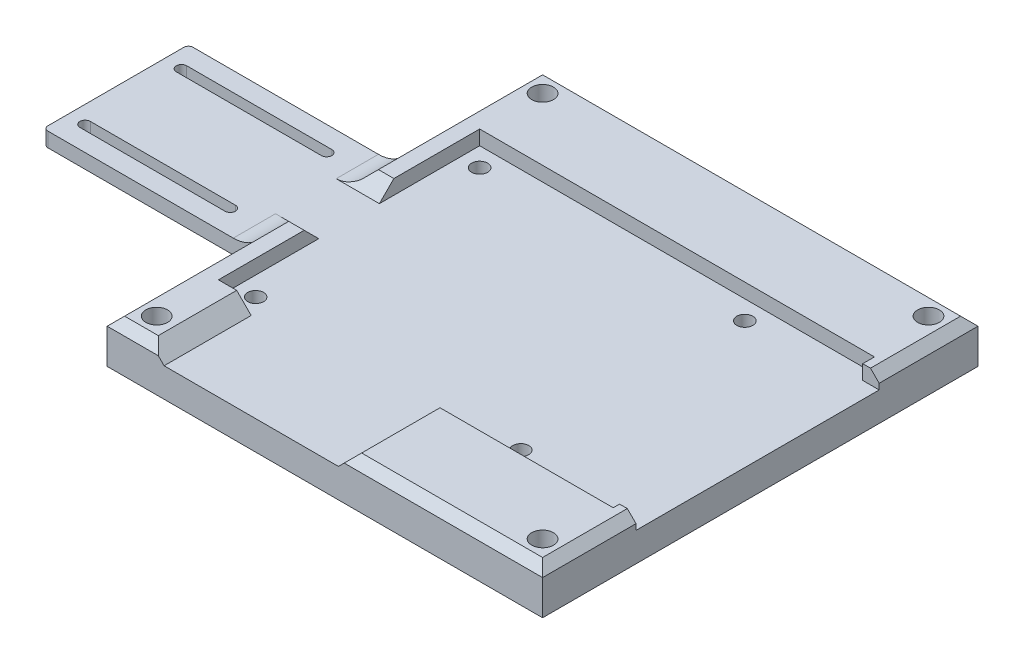
SolidWorks part; units mm, degrees
material "ABS"
ref_plane "Front Plane" through (0, 0, 0) normal (0, 0, 1) x (1, 0, 0)
ref_plane "Top Plane" through (0, 0, 0) normal (0, 1, 0) x (1, 0, 0)
ref_plane "Right Plane" through (0, 0, 0) normal (1, 0, 0) x (0, 0, -1)
sketch "Sketch1" plane through (0, 0, 0) normal (0, 1, 0) x (1, 0, 0)
  line L1 (-47.625, 47.625) -> (47.625, 47.625)
  line L2 (-47.625, 47.625) -> (-47.625, -47.625)
  line L3 (-47.625, -47.625) -> (47.625, -47.625)
  line L4 (47.625, 47.625) -> (47.625, -47.625)
  line L5 (-47.625, 47.625) -> (47.625, -47.625) construction
  line L6 (-47.625, -47.625) -> (47.625, 47.625) construction
  point P0 (0, 0)
  dimension "D1" = 95.25
  dimension "D2" = 95.25
extrude "Base Extrude" add sketch "Sketch1" along normal blind 6.35
sketch "Sketch2" plane through (0, 6.35, 0) normal (0, 1, 0) x (1, 0, 0)
  line L0 (-47.625, 0) -> (47.625, 0) construction
  line L1 (-42.3368, -28.575) -> (-34.5346, -28.575)
  line L2 (-42.3368, -28.575) -> (-42.3368, -6)
  line L3 (-42.3368, 28.575) -> (44.0232, 28.575)
  line L4 (44.0232, -28.575) -> (44.0232, -27.1833)
  line L5 (-47.625, 47.625) -> (-47.625, -47.625) construction
  line L6 (47.625, -47.625) -> (47.625, 47.625) construction
  line L7 (-42.3368, 6) -> (-47.625, 6)
  line L8 (-47.625, 47.625) -> (47.625, 47.625)
  line L9 (-47.625, 47.625) -> (-47.625, -47.625)
  line L10 (-47.625, -47.625) -> (47.625, -47.625)
  line L11 (47.625, 47.625) -> (47.625, -47.625)
  line L12 (-42.3368, -6) -> (-47.625, -6)
  line L13 (-47.625, -6) -> (-47.625, 6)
  line L14 (-42.3368, 6) -> (-42.3368, 28.575)
  line L15 (44.0232, 26.0091) -> (47.625, 26.0091)
  line L16 (44.0232, -27.1833) -> (47.625, -27.1833)
  line L17 (47.625, 26.0091) -> (47.625, -27.1833)
  line L18 (44.0232, 26.0091) -> (44.0232, 28.575)
  line L19 (-34.5346, -28.575) -> (-34.5346, -50.5748)
  line L20 (2.3256, -28.575) -> (2.3256, -50.5748)
  line L21 (2.3256, -50.5748) -> (-34.5346, -50.5748)
  line L22 (2.3256, -28.575) -> (44.0232, -28.575)
  point P24 (-47.625, 0)
  line M6 (47.625, -47.625) -> (47.625, 47.625)
  line M7 (47.625, 47.625) -> (-47.625, 47.625)
  line M8 (-47.625, 47.625) -> (-47.625, -47.625)
  line M9 (-47.625, -47.625) -> (47.625, -47.625)
  dimension "D1" = 86.36
  dimension "D2" = 57.15
  dimension "D3" = 12
  dimension "D4" = 53.1924
extrude "Pi Slot" add sketch "Sketch2" along normal blind 3.175 contours L19 L1 L2 L12 L9 M9 | L22 L20 L16 L4 M9 M6 | L18 L15 L11 L7 L14 L3 M7 M8
chamfer "Chamfer1" distance 3.81 angle 45 4 edges at (2.3256, 9.525, 38.1) (-34.5346, 9.525, 38.1) (-44.9809, 9.525, 6) (-44.9809, 9.525, -6)
chamfer "Chamfer2" distance 1.905 angle 45 7 edges at (47.625, 9.525, -36.8171) (0, 9.525, -47.625) (-47.625, 9.525, -28.7175) (-47.625, 9.525, 28.7175) (-42.9848, 9.525, 47.625) (47.625, 9.525, 37.4041) (26.8803, 9.525, 47.625)
sketch "Sketch3" plane through (0, 0, 0) normal (0, 1, 0) x (1, 0, 0)
  line L0 (-47.625, -47.625) -> (-47.625, -7.905) construction
  line L1 (-93.345, 15.875) -> (-47.625, 15.875)
  line L2 (-93.345, 15.875) -> (-93.345, -15.875)
  line L3 (-93.345, -15.875) -> (-47.625, -15.875)
  line L4 (-47.625, 15.875) -> (-47.625, -15.875)
  line L5 (-93.345, 15.875) -> (-47.625, -15.875) construction
  line L6 (-93.345, -15.875) -> (-47.625, 15.875) construction
  line L7 (-47.625, 0) -> (-93.345, 0) construction
  line L8 (-89.535, 10.541) -> (-57.785, 10.541) construction
  line L9 (-89.535, 11.684) -> (-57.785, 11.684)
  line L10 (-89.535, 9.398) -> (-57.785, 9.398)
  line L11 (0, 0) -> (-47.625, 0) construction
  line L13 (-89.535, -10.541) -> (-57.785, -10.541) construction
  line L14 (-89.535, -11.684) -> (-57.785, -11.684)
  line L15 (-89.535, -9.398) -> (-57.785, -9.398)
  arc A0 (-89.535, 11.684) -> (-89.535, 9.398) centre (-89.535, 10.541) ccw
  arc A1 (-57.785, 9.398) -> (-57.785, 11.684) centre (-57.785, 10.541) ccw
  arc A2 (-89.535, -11.684) -> (-89.535, -9.398) centre (-89.535, -10.541) cw
  arc A3 (-57.785, -9.398) -> (-57.785, -11.684) centre (-57.785, -10.541) cw
  point P0 (-70.485, 0)
  point P11 (-73.66, 10.541)
  point P23 (-73.66, -10.541)
  dimension "D4" = 1.143
  dimension "D6" = 10.16
  dimension "D1" = 45.72
  dimension "D2" = 31.75
  dimension "D3" = 10.541
  dimension "D5" = 31.75
extrude "Camera Slot" add sketch "Sketch3" against normal blind 3.175 from surface at 6.35 starting at face at (-3.6045, 6.35, 9.6718)
fillet "Fillet1" radius 1 2 edges at (-93.345, 4.7625, 15.875) (-93.345, 4.7625, -15.875)
chamfer "Chamfer3" distance 1.905 angle 64 1 edges at (-47.625, 3.175, 0)
fillet "Fillet2" radius 7.46 2 edges at (-47.625, 6.35, -11.255) (-47.625, 6.35, 11.255)
sketch "Mounting Spots" plane through (0, 9.525, 0) normal (0, 1, 0) x (1, 0, 0)
  line L0 (-47.625, 47.625) -> (47.625, -47.625) construction
  line L1 (-47.625, -47.625) -> (47.625, 47.625) construction
  circle A0 centre (0, 0) radius 59.69 construction
  circle A1 centre (42.2072, 42.2072) radius 3.8405
  circle A2 centre (-42.2072, 42.2072) radius 3.8405
  circle A3 centre (-42.2072, -42.2072) radius 3.8405
  circle A4 centre (42.2072, -42.2072) radius 3.8405
  dimension "D1" = 119.38
  dimension "D2" = 7.681
hole_wizard "3/16 (0.1875) Diameter Hole1" positions "Sketch7" profile "Sketch8" hole size "3/16" standard "ANSI Inch"
sketch "Sketch7" plane through (0, 9.525, 0) normal (0, 1, 0) x (1, 0, 0)
  point P0 (-42.2072, 42.2072)
  point P3 (42.2072, 42.2072)
  point P6 (42.2072, -42.2072)
  point P9 (-42.2072, -42.2072)
sketch "Sketch8" plane through (-42.2072, 9.525, -42.2072) normal (1, 0, 0) x (0, 0, 1)
  line L0 (0, 0) -> (0, 10.9558)
  line L1 (0, 10.9558) -> (2.3812, 9.525)
  line L2 (2.3812, 9.525) -> (2.3812, 0)
  line L5 (2.3812, 0) -> (0, 0)
  line L10 (0, 10.9558) -> (-2.3813, 9.525) construction
  line L11 (0, -6.35) -> (0, 107.95) construction
  dimension "Hole Dia." = 4.7625
  dimension "Hole Depth" = 9.525
  dimension "Drill Angle" = 118
sketch "PiBoardHoles" plane through (0, 6.35, 0) normal (0, 1, 0) x (1, 0, 0)
  line L0 (-42.3368, 9.81) -> (-42.3368, 28.575) construction
  line L1 (-42.3368, 28.575) -> (44.0232, 28.575) construction
  circle A0 centre (-38.1784, 24.41) radius 1.1 construction
  circle A1 centre (19.8216, 24.41) radius 1.1 construction
  circle A2 centre (-38.1784, -24.59) radius 1.1
  circle A3 centre (19.8216, -24.59) radius 1.1
  dimension "D4" = 2.2
  dimension "D1" = 4.1584
  dimension "D2" = 4.165
  dimension "D3" = 58
  dimension "D5" = 49
hole_wizard "Ø3.5 (3.5) Diameter Hole1" positions "Sketch14" profile "Sketch15" hole size "Ø3.5" standard "ANSI Metric"
sketch "Sketch14" plane through (0, 6.35, 0) normal (0, 1, 0) x (1, 0, 0)
  point P0 (-38.1784, 24.41)
  point P3 (19.8216, 24.41)
  point P6 (19.8216, -24.59)
  point P9 (-38.1784, -24.59)
sketch "Sketch15" plane through (-38.1784, 6.35, -24.41) normal (1, 0, 0) x (0, 0, 1)
  line L0 (0, 0) -> (0, 5.1155)
  line L1 (0, 5.1155) -> (1.75, 4.064)
  line L2 (1.75, 4.064) -> (1.75, 0)
  line L5 (1.75, 0) -> (0, 0)
  line L10 (0, 5.1155) -> (-1.75, 4.064) construction
  line L11 (0, -6.35) -> (0, 107.95) construction
  dimension "Hole Dia." = 3.5
  dimension "Hole Depth" = 4.064
  dimension "Drill Angle" = 118
equation "\"MSquare\"= 3.75"
equation "\"D1@Sketch1\"=\"MSquare\""
equation "\"D2@Sketch1\"=\"MSquare\""
equation "\"MountHoleDist\"= 4.7"
equation "\"D1@Mounting Spots\" = \"MountHoleDist\""
equation "\"MountHoleSize\"=0.302401"
equation "\"D2@Mounting Spots\" = \"MountHoleSize\""
